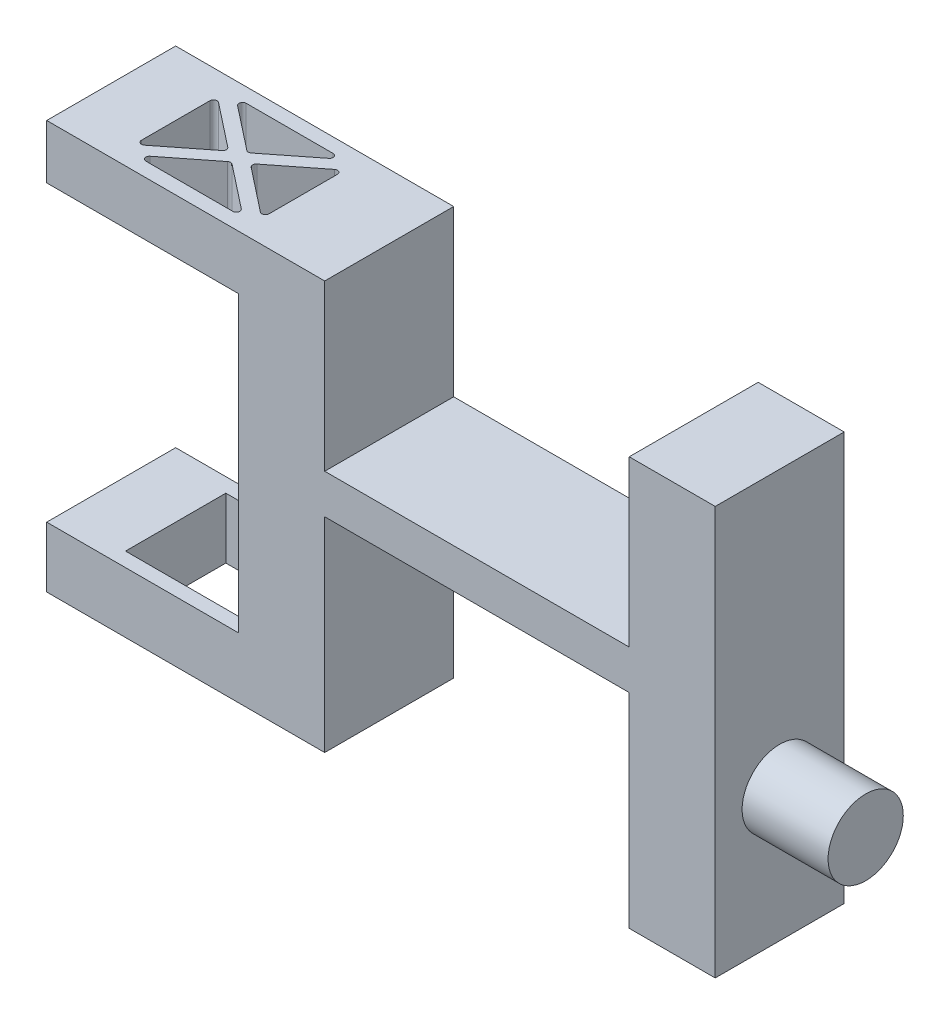
SolidWorks part; units mm, degrees
material "PLA"
ref_plane "Front Plane" through (0, 0, 0) normal (0, 0, 1) x (1, 0, 0)
ref_plane "Top Plane" through (0, 0, 0) normal (0, 1, 0) x (1, 0, 0)
ref_plane "Right Plane" through (0, 0, 0) normal (1, 0, 0) x (0, 0, -1)
sketch "Sketch2" plane through (0, 0, 0) normal (0, 0, 1) x (1, 0, 0)
  line L0 (0, -55) -> (0, 55) construction
  line L1 (0, 55) -> (66.5, 55)
  line L2 (0, 55) -> (0, 0)
  line L3 (0, 0) -> (66.5, 0)
  line L4 (66.5, 55) -> (66.5, 0)
  line L5 (55, 0) -> (-55, 0) construction
  line L7 (12, 50.75) -> (54.5, 50.75)
  line L8 (12, 50.75) -> (12, 30.25)
  line L9 (12, 30.25) -> (54.5, 30.25)
  line L10 (54.5, 50.75) -> (54.5, 30.25)
  line L11 (12, 24.75) -> (54.5, 24.75)
  line L12 (12, 24.75) -> (12, 4.25)
  line L13 (12, 4.25) -> (54.5, 4.25)
  line L14 (54.5, 24.75) -> (54.5, 4.25)
  dimension "D1" = 55
  dimension "D2" = 12
  dimension "D3" = 42.5
  dimension "D4" = 20.5
  dimension "D5" = 5.5
  dimension "D6" = 42.5
  dimension "D7" = 20.5
  dimension "D8" = 12
  dimension "D9" = 4.25
  dimension "D10" = 12
extrude "Boss-Extrude1" add sketch "Sketch2" along normal blind 18
sketch "Sketch3" plane through (0, 0, 18) normal (0, 0, 1) x (1, 0, 0)
  line L2 (12, 24.75) -> (12, 4.25) construction
  line L3 (54.5, 24.75) -> (12, 24.75) construction
  circle A8 centre (8.15, 19.75) radius 2.5
  circle A9 centre (8.15, 9.75) radius 2.5
  circle A10 centre (57.85, 9.75) radius 2.5
  circle A11 centre (57.85, 19.75) radius 2.5
  dimension "D9" = 45.85
  dimension "D10" = 45.85
  dimension "D11" = 5
  dimension "D12" = 5
  dimension "D13" = 3.85
  dimension "D14" = 3.85
  dimension "D15" = 10
  dimension "D16" = 5
  dimension "D17" = 5
  dimension "D18" = 5
  dimension "D19" = 5
  dimension "D24" = 10
sketch "Sketch5" plane through (0, 0, 0) normal (-1, 0, 0) x (0, 0, 1)
  line L0 (0, -55) -> (0, 55) construction
  line L1 (0, 55) -> (2, 55)
  line L2 (0, 55) -> (0, 49)
  line L3 (0, 49) -> (2, 49)
  line L4 (2, 55) -> (2, 49)
  line L5 (18, 55) -> (0, 55) construction
  line L6 (55, 0) -> (-55, 0) construction
  line L7 (18, 55) -> (16, 55)
  line L8 (18, 55) -> (18, 49)
  line L9 (18, 49) -> (16, 49)
  line L10 (16, 55) -> (16, 49)
  line L11 (0, 0) -> (2, 0)
  line L12 (0, 0) -> (0, 6)
  line L13 (0, 6) -> (2, 6)
  line L14 (2, 0) -> (2, 6)
  line L15 (18, 0) -> (16, 0)
  line L16 (18, 0) -> (18, 6)
  line L17 (18, 6) -> (16, 6)
  line L18 (16, 0) -> (16, 6)
  line L19 (18, 55) -> (18, 0) construction
  dimension "D1" = 2
  dimension "D2" = 2
  dimension "D3" = 6
  dimension "D4" = 6
  dimension "D5" = 2
  dimension "D6" = 2
  dimension "D7" = 6
  dimension "D8" = 6
extrude "Boss-Extrude2" add sketch "Sketch5" along normal blind 26.8
sketch "Sketch6" plane through (0, 0, 2) normal (0, 0, 1) x (1, 0, 0)
  line L0 (-26.8, 49) -> (0, 49) construction
  line L1 (-23.8, 49) -> (-26.8, 49)
  line L2 (-23.8, 49) -> (-23.8, 55)
  line L3 (-23.8, 55) -> (-26.8, 55)
  line L4 (-26.8, 49) -> (-26.8, 55)
  line L5 (66.5, 55) -> (-26.8, 55) construction
  line L6 (-26.8, 55) -> (-26.8, 49) construction
  line L7 (55, 0) -> (-55, 0) construction
  line L8 (-26.8, 6) -> (-24.8, 6)
  line L9 (-26.8, 6) -> (-26.8, 0)
  line L10 (-26.8, 0) -> (-24.8, 0)
  line L11 (-24.8, 6) -> (-24.8, 0)
  dimension "D1" = 3
  dimension "D2" = 2
extrude "Boss-Extrude3" add sketch "Sketch6" along normal up to next
sketch "Sketch8" plane through (0, 0, 18) normal (0, 0, 1) x (1, 0, 0)
  line L0 (66.5, 55) -> (-26.8, 55) construction
  line L1 (12, 50.75) -> (54, 50.75)
  line L2 (12, 50.75) -> (12, 55)
  line L3 (12, 55) -> (54, 55)
  line L4 (54, 50.75) -> (54, 55)
  line L5 (55, 0) -> (-55, 0) construction
  line L6 (12, 4.25) -> (54.5, 4.25)
  line L7 (12, 4.25) -> (12, 0)
  line L8 (12, 0) -> (54.5, 0)
  line L9 (54.5, 4.25) -> (54.5, 0)
extrude "Cut-Extrude3" cut sketch "Sketch8" against normal up to next
sketch "Sketch12" plane through (0, 0, 2) normal (0, 0, 1) x (1, 0, 0)
  line L0 (-26.8, 6) -> (0, 6) construction
  line L1 (-8, 6) -> (-5, 6)
  line L2 (-8, 6) -> (-8, 0)
  line L3 (-8, 0) -> (-5, 0)
  line L4 (-5, 6) -> (-5, 0)
  line L5 (55, 0) -> (-55, 0) construction
  line L6 (0, -55) -> (0, 55) construction
  dimension "D1" = 3
  dimension "D2" = 5
extrude "Boss-Extrude7" add sketch "Sketch12" along normal up to surface (14 mm away) up to face at (-12.4, 3, 16)
sketch "Sketch14" plane through (-8, 0, 0) normal (-1, 0, 0) x (0, 0, 1)
  line L0 (18, 6) -> (0, 6) construction
  line L1 (7, 6) -> (11, 6)
  line L2 (7, 6) -> (7, 0)
  line L3 (7, 0) -> (11, 0)
  line L4 (11, 6) -> (11, 0)
  line L5 (55, 0) -> (-55, 0) construction
  line L6 (0, -55) -> (0, 55) construction
  line L7 (18, 0) -> (18, 6) construction
  dimension "D1" = 7
  dimension "D2" = 7
extrude "Boss-Extrude8" add sketch "Sketch14" along normal up to surface (16.8 mm away) up to face at (-24.8, 3, 9)
sketch "Sketch17" plane through (0, 0, 2) normal (0, 0, 1) x (1, 0, 0)
  line L1 (-23.8, 55) -> (0, 55)
  line L2 (-23.8, 55) -> (-23.8, 49)
  line L3 (-23.8, 49) -> (0, 49)
  line L4 (0, 55) -> (0, 49)
extrude "Boss-Extrude9" add sketch "Sketch17" along normal blind 14 and the other way blind 1
sketch "Sketch18" plane through (0, 6, 0) normal (0, 1, 0) x (1, 0, 0)
  line L1 (-5, -2) -> (-24.8, -2)
  line L2 (-5, -2) -> (-5, -16)
  line L3 (-5, -16) -> (-24.8, -16)
  line L4 (-24.8, -2) -> (-24.8, -16)
extrude "Cut-Extrude4" cut sketch "Sketch18" against normal blind 10
sketch "Sketch20" plane through (0, 6, 0) normal (0, 1, 0) x (1, 0, 0)
  line L0 (-24.8, -16) -> (0, -16) construction
  line L1 (-24.8, -2) -> (-19.8, -2)
  line L2 (-24.8, -2) -> (-24.8, -16)
  line L3 (-24.8, -16) -> (-19.8, -16)
  line L4 (-19.8, -2) -> (-19.8, -16)
  dimension "D1" = 5
extrude "Boss-Extrude10" add sketch "Sketch20" against normal blind 6
sketch "Sketch22" plane through (0, 55, 0) normal (0, 1, 0) x (1, 0, 0)
  line L0 (-55, 0) -> (55, 0) construction
  line L1 (-26.8, -18) -> (12, -18)
  line L2 (-26.8, -18) -> (-26.8, 0)
  line L3 (-26.8, 0) -> (12, 0)
  line L4 (12, -18) -> (12, 0)
  line L5 (12, -18) -> (12, 0) construction
extrude "Boss-Extrude11" add sketch "Sketch22" along normal blind 1
sketch "Sketch23" plane through (0, 49, 0) normal (0, -1, 0) x (1, 0, 0)
  line L1 (0, 18) -> (-26.8, 18)
  line L2 (0, 18) -> (0, 0)
  line L3 (0, 0) -> (-26.8, 0)
  line L4 (-26.8, 18) -> (-26.8, 0)
extrude "Boss-Extrude12" add sketch "Sketch23" along normal blind 1
sketch "Sketch24" plane through (0, 6, 0) normal (0, 1, 0) x (1, 0, 0)
  line L0 (0, 0) -> (-26.8, 0)
  line L1 (-26.8, 0) -> (-26.8, -18)
  line L2 (-26.8, -18) -> (0, -18)
  line L3 (0, -18) -> (0, -16)
  line L4 (0, -16) -> (-19.8, -16)
  line L5 (-19.8, -16) -> (-19.8, -2)
  line L6 (-19.8, -2) -> (0, -2)
  line L7 (0, -2) -> (0, 0)
extrude "Boss-Extrude13" add sketch "Sketch24" along normal blind 1
sketch "Sketch25" plane through (0, 55, 0) normal (0, 1, 0) x (1, 0, 0)
  line L0 (-55, 0) -> (55, 0) construction
  line L1 (66.5, -18) -> (54.5, -18)
  line L2 (66.5, -18) -> (66.5, 0)
  line L3 (66.5, 0) -> (54.5, 0)
  line L4 (54.5, -18) -> (54.5, 0)
  line L5 (54.5, -18) -> (54.5, 0) construction
extrude "Boss-Extrude14" add sketch "Sketch25" along normal blind 1
sketch "Sketch27" plane through (0, 0, 0) normal (0, -1, 0) x (1, 0, 0)
  line L0 (-26.8, 18) -> (12, 18)
  line L1 (12, 18) -> (12, 0)
  line L2 (55, 0) -> (-55, 0) construction
  line L3 (12, 18) -> (12, 0) construction
  line L4 (12, 0) -> (-26.8, 0)
  line L5 (-26.8, 0) -> (-26.8, 18) construction
  line L6 (-26.8, 0) -> (-26.8, 18)
  line L7 (-19.8, 16) -> (-19.8, 2)
  line L8 (-19.8, 2) -> (0, 2)
  line L9 (0, 2) -> (0, 16)
  line L10 (0, 16) -> (0, 2) construction
  line L11 (-19.8, 16) -> (0, 16) construction
  line L12 (0, 16) -> (-19.8, 16)
extrude "Boss-Extrude15" add sketch "Sketch27" along normal blind 1
sketch "Sketch28" plane through (0, 0, 0) normal (0, -1, 0) x (1, 0, 0)
  line L0 (55, 0) -> (-55, 0) construction
  line L1 (54.5, 18) -> (66.5, 18)
  line L2 (54.5, 18) -> (54.5, 0)
  line L3 (54.5, 0) -> (66.5, 0)
  line L4 (66.5, 18) -> (66.5, 0)
  line L5 (66.5, 18) -> (66.5, 0) construction
extrude "Boss-Extrude16" add sketch "Sketch28" along normal blind 1
sketch "Sketch32" plane through (-26.8, 0, 0) normal (-1, 0, 0) x (0, 0, 1)
  line L0 (0, -55) -> (0, 55) construction
  line L1 (18, 7) -> (0, 7)
  line L2 (18, 7) -> (18, 4.25)
  line L3 (18, 4.25) -> (0, 4.25)
  line L4 (0, 7) -> (0, 4.25)
  dimension "D1" = 2.75
extrude "Cut-Extrude8" cut sketch "Sketch32" against normal blind 26.8
sketch "Sketch33" plane through (0, -1, 0) normal (0, -1, 0) x (1, 0, 0)
  line L0 (-26.8, 18) -> (12, 18)
  line L1 (12, 18) -> (12, 0)
  line L2 (31.35, 0) -> (-31.35, 0) construction
  line L3 (12, 18) -> (12, 0) construction
  line L4 (12, 0) -> (-26.8, 0)
  line L5 (-26.8, 18) -> (-26.8, 0) construction
  line L6 (-26.8, 0) -> (-26.8, 18)
  line L7 (-19.8, 16) -> (0, 16)
  line L8 (0, -9.9) -> (0, 9.9) construction
  line L9 (0, 16) -> (-19.8, 16) construction
  line L10 (0, 16) -> (0, 2)
  line L11 (0, 2) -> (-19.8, 2)
  line L12 (-19.8, 2) -> (-19.8, 16)
extrude "Boss-Extrude17" add sketch "Sketch33" along normal blind 2.75
sketch "Sketch34" plane through (0, -1, 0) normal (0, -1, 0) x (1, 0, 0)
  line L0 (31.35, 0) -> (-31.35, 0) construction
  line L1 (54.5, 18) -> (66.5, 18)
  line L2 (54.5, 18) -> (54.5, 0)
  line L3 (54.5, 0) -> (66.5, 0)
  line L4 (66.5, 18) -> (66.5, 0)
  line L5 (66.5, 0) -> (66.5, 18) construction
extrude "Boss-Extrude18" add sketch "Sketch34" along normal blind 2.75
sketch "Sketch35" plane through (0, 48, 0) normal (0, -1, 0) x (1, 0, 0)
  line L1 (-26.8, 18) -> (0, 18)
  line L2 (-26.8, 18) -> (-26.8, 0)
  line L3 (-26.8, 0) -> (0, 0)
  line L4 (0, 18) -> (0, 0)
extrude "Boss-Extrude19" add sketch "Sketch35" along normal blind 2.3
sketch "Sketch36" plane through (0, 56, 0) normal (0, 1, 0) x (1, 0, 0)
  line L0 (-31.35, 0) -> (31.35, 0) construction
  line L1 (66.5, -18) -> (54.5, -18)
  line L2 (66.5, -18) -> (66.5, 0)
  line L3 (66.5, 0) -> (54.5, 0)
  line L4 (54.5, -18) -> (54.5, 0)
  line L5 (54.5, -18) -> (54.5, 0) construction
  line L7 (12, -18) -> (-26.8, -18)
  line L8 (12, -18) -> (12, 0)
  line L9 (12, 0) -> (-26.8, 0)
  line L10 (-26.8, -18) -> (-26.8, 0)
extrude "Cut-Extrude9" cut sketch "Sketch36" against normal blind 2.75
sketch "Sketch37" plane through (-26.8, 0, 0) normal (-1, 0, 0) x (0, 0, 1)
  line L0 (0, 53.25) -> (18, 53.25) construction
  line L1 (0, -31.35) -> (0, 31.35) construction
  line L2 (18, 45.7) -> (18, 53.25) construction
  circle A0 centre (4, 49.45) radius 2.5
  circle A1 centre (14, 49.45) radius 2.5
  dimension "D1" = 3.8
  dimension "D2" = 4
  dimension "D3" = 4
  dimension "D4" = 3.8
  dimension "D5" = 5
  dimension "D6" = 5
sketch "Sketch38" plane through (-26.8, 0, 0) normal (-1, 0, 0) x (0, 0, 1)
  line L0 (0, 4.25) -> (18, 4.25) construction
  line L1 (0, -31.35) -> (0, 31.35) construction
  line L2 (18, -3.75) -> (18, 4.25) construction
  circle A0 centre (4, 0.45) radius 2.5
  circle A1 centre (14, 0.45) radius 2.5
  dimension "D1" = 3.8
  dimension "D2" = 5
  dimension "D3" = 4
  dimension "D4" = 5
  dimension "D5" = 4
  dimension "D6" = 3.8
extrude "Cut-Extrude10" cut sketch "Sketch37" against normal blind 6
sketch "Sketch39" plane through (0, 0, 0) normal (0, 0, -1) x (-1, 0, 0)
  line L0 (-54.5, 30.25) -> (-54.5, 27.5) construction
  line L2 (-54.5, 27.5) -> (-66.5, 27.5) construction
  line L3 (-66.5, -3.75) -> (-66.5, 53.25) construction
  circle A2 centre (-8.15, 19.75) radius 2.5
  circle A3 centre (-8.15, 9.75) radius 2.5
  circle A6 centre (-57.85, 19.75) radius 2.5
  circle A7 centre (-57.85, 9.75) radius 2.5
  circle A8 centre (-8.15, 45.25) radius 2.5
  circle A9 centre (-8.15, 35.25) radius 2.5
  circle A10 centre (-57.85, 45.25) radius 2.5
  circle A11 centre (-57.85, 35.25) radius 2.5
  dimension "D1" = 2.75
  dimension "D4" = 5
  dimension "D5" = 5
  dimension "D6" = 5
  dimension "D7" = 5
extrude "Cut-Extrude12" cut sketch "Sketch39" against normal blind 10
extrude "Cut-Extrude11" cut sketch "Sketch38" against normal blind 6
sketch "Sketch40" plane through (0, 0, 0) normal (0, 0, -1) x (-1, 0, 0)
  line L0 (-57.85, 35.25) -> (-8.15, 35.25) construction
  line L1 (-57.85, 19.75) -> (-8.15, 19.75) construction
  line L3 (-54, 50.75) -> (-54.5, 50.75)
  line L4 (-54, 50.75) -> (-54, 55)
  line L5 (-54, 55) -> (-54.5, 55)
  line L6 (-54.5, 50.75) -> (-54.5, 55)
extrude "Cut-Extrude13" cut sketch "Sketch40" against normal up to surface (18 mm away) up to face at (25.44, 30.97, 18)
sketch "Sketch43" plane through (0, 4.25, 0) normal (0, 1, 0) x (1, 0, 0)
  line L0 (0, 0) -> (-26.8, 0)
  line L1 (-26.8, 0) -> (-26.8, -18)
  line L2 (-26.8, -18) -> (0, -18)
  line L3 (0, -18) -> (0, -16)
  line L4 (0, -16) -> (-19.8, -16)
  line L5 (-19.8, -16) -> (-19.8, -2)
  line L6 (-19.8, -2) -> (0, -2)
  line L7 (0, -2) -> (0, 0)
extrude "Boss-Extrude21" add sketch "Sketch43" along normal blind 0.45
sketch "Sketch44" plane through (66.5, 0, 0) normal (1, 0, 0) x (0, 0, -1)
  line L0 (0, -3.75) -> (-18, -3.75) construction
  line L1 (-18, -3.75) -> (-18, 53.25) construction
  circle A0 centre (-9, 14.75) radius 5.25
  dimension "D1" = 10.5
  dimension "D2" = 18.5
  dimension "D3" = 9
extrude "Boss-Extrude22" add sketch "Sketch44" along normal blind 12
sketch "Sketch45" plane through (-19.8, 0, 0) normal (1, 0, 0) x (0, 0, -1)
  line L1 (-16, 4.7) -> (-2, 4.7)
  line L2 (-16, 4.7) -> (-16, -3.75)
  line L3 (-16, -3.75) -> (-2, -3.75)
  line L4 (-2, 4.7) -> (-2, -3.75)
  line L5 (-16, 4.7) -> (-2, -3.75) construction
  line L6 (-16, -3.75) -> (-2, 4.7) construction
  point P4 (-9, 0.475)
extrude "Boss-Extrude23" add sketch "Sketch45" along normal blind 2
sketch "Sketch48" plane through (0, 45.7, 0) normal (0, -1, 0) x (-1, 0, 0)
  line L0 (17.8, -16) -> (0, -2) construction
  line L1 (17.8, -16) -> (0, -16) construction
  line L2 (17.8, -16) -> (17.8, -2) construction
  line L3 (17.8, -2) -> (0, -2) construction
  line L4 (0, -16) -> (0, -2) construction
  line L5 (0, -16) -> (17.8, -2) construction
  line L6 (8.9, -16) -> (8.9, -2) construction
  line L7 (17.8, -9) -> (0, -9) construction
  line L8 (8.9, -16) -> (1.4, -16)
  line L9 (1.4, -16) -> (8.9, -10.1012)
  line L10 (8.9, -10.1012) -> (16.4, -16)
  line L11 (16.4, -16) -> (8.9, -16)
  line L12 (1.3986, -2) -> (8.9, -7.9)
  line L13 (8.9, -7.9) -> (16.4014, -2)
  line L14 (16.4014, -2) -> (1.3986, -2)
  line L15 (0, -9) -> (0, -3.2)
  line L16 (0, -3.2) -> (7.3743, -9)
  line L17 (7.3743, -9) -> (0, -14.8)
  line L18 (0, -14.8) -> (0, -3.2)
  line L19 (17.8, -3.1959) -> (10.4205, -9)
  line L20 (10.4205, -9) -> (17.8, -14.8041)
  line L21 (17.8, -14.8041) -> (17.8, -3.1959)
  point P15 (8.9, -9)
  dimension "D1" = 7.5
  dimension "D2" = 7.5
  dimension "D3" = 1.1
  dimension "D4" = 5.8
  dimension "D5" = 0.94
extrude "Cut-Extrude14" cut sketch "Sketch48" against normal through all contours L14 L12 L13 | L16 L17 L18 | L21 L19 L20 | L11 L8 L9 L10
fillet "Fillet1" radius 0.5 12 edges at (-1.3986, 49.475, 2) (-16.4014, 49.475, 2) (-17.8, 49.475, 3.1959) (-10.4205, 49.475, 9) (-17.8, 49.475, 14.8041) (-16.4, 49.475, 16) (-1.4, 49.475, 16) (-8.9, 49.475, 10.1012) (-7.3743, 49.475, 9) (0, 49.475, 3.2) (0, 49.475, 14.8) (-8.9, 49.475, 7.9)
